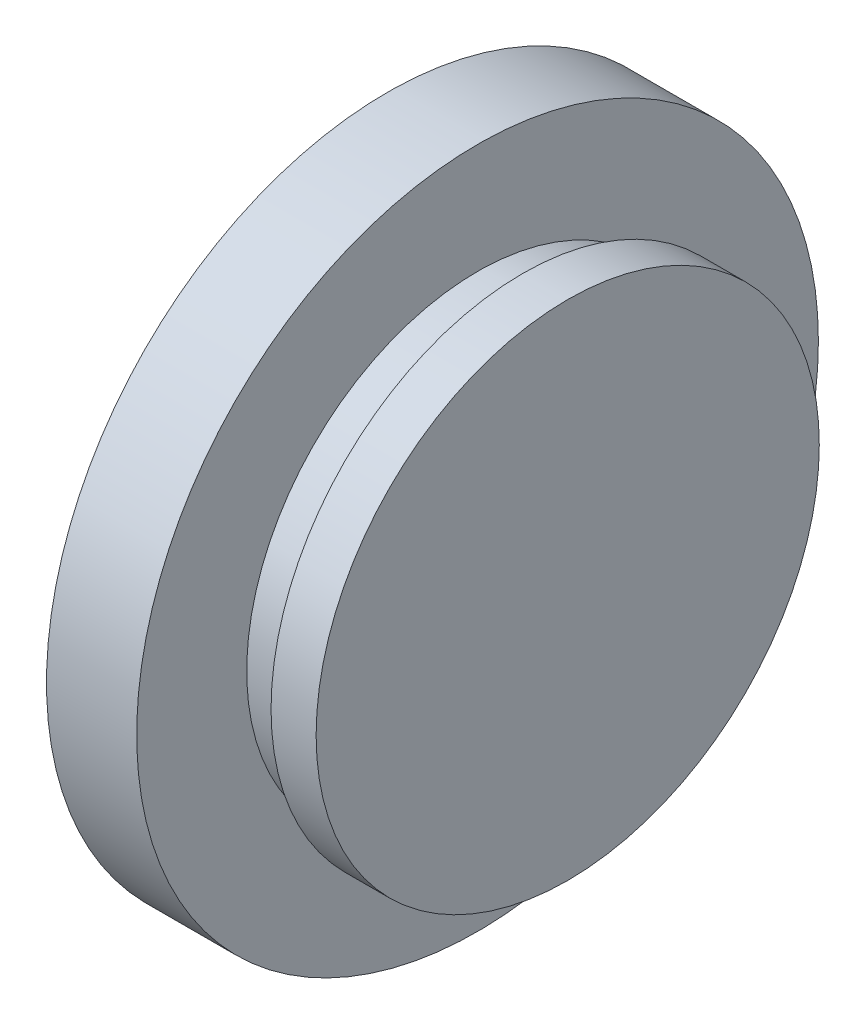
SolidWorks part; units mm, degrees
ref_plane "Front Plane" through (0, 0, 0) normal (0, 0, 1) x (1, 0, 0)
ref_plane "Top Plane" through (0, 0, 0) normal (0, 1, 0) x (1, 0, 0)
ref_plane "Right Plane" through (0, 0, 0) normal (1, 0, 0) x (0, 0, -1)
sketch "Sketch2" plane through (0, 0, 0) normal (1, 0, 0) x (0, 0, -1)
  circle A0 centre (0, 0) radius 17.9
  circle A1 centre (0, 0) radius 12.8
  circle A2 centre (0, 0) radius 18.9
  dimension "D1" = 35.8
  dimension "D2" = 25.6
  dimension "D3" = 37.8
extrude "Boss-Extrude1" add sketch "Sketch2" along normal blind 5 contours A2
extrude "Cut-Extrude1" cut sketch "Sketch2<4>" along normal blind 3.95 contours A0
sketch "Sketch2<4>" plane through (0, 0, 0) normal (1, 0, 0) x (0, 0, -1) same geometry as "Sketch2"
sketch "Sketch7" plane through (5, 0, 0) normal (1, 0, 0) x (0, 0, -1)
  circle A0 centre (0, 0) radius 12.8
  dimension "D1" = 25.6
extrude "Boss-Extrude2" add sketch "Sketch7" along normal blind 2.5
sketch "Sketch8" plane through (7.5, 0, 0) normal (1, 0, 0) x (0, 0, -1)
  circle A0 centre (0, 0) radius 13.95
  dimension "D1" = 27.9
extrude "Boss-Extrude3" add sketch "Sketch8" along normal blind 2.5
